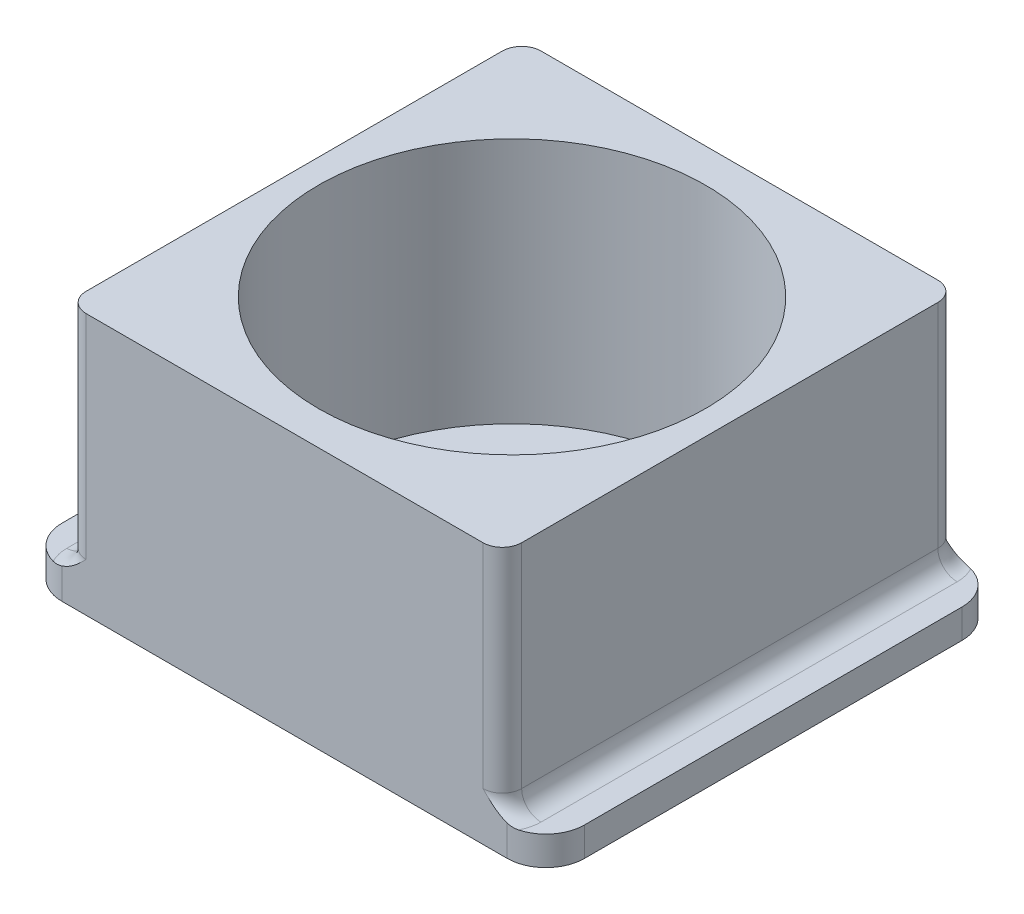
SolidWorks part; units mm, degrees
material "灰铸铁 HT200 (GB)"
ref_plane "前视基准面" through (0, 0, 0) normal (0, 0, 1) x (1, 0, 0)
ref_plane "上视基准面" through (0, 0, 0) normal (0, 1, 0) x (1, 0, 0)
ref_plane "右视基准面" through (0, 0, 0) normal (1, 0, 0) x (0, 0, -1)
sketch "草图1" plane through (0, 0, 0) normal (0, 1, 0) x (1, 0, 0)
  line L1 (-27, -23.5) -> (27, -23.5)
  line L2 (-27, -23.5) -> (-27, 23.5)
  line L3 (-27, 23.5) -> (27, 23.5)
  line L4 (27, -23.5) -> (27, 23.5)
  line L5 (-27, -23.5) -> (27, 23.5) construction
  line L6 (-27, 23.5) -> (27, -23.5) construction
  point P0 (0, 0)
  dimension "D1" = 47
  dimension "D2" = 54
extrude "凸台-拉伸1" add sketch "草图1" along normal mid plane 3
fillet "圆角1" radius 4 4 edges at (27, 0, 23.5) (-27, 0, 23.5) (-27, 0, -23.5) (27, 0, -23.5)
sketch "草图2" plane through (0, 1.5, 0) normal (0, 1, 0) x (1, 0, 0)
  line L1 (-20.5, -23.5) -> (20.5, -23.5)
  line L2 (-22.5, -21.5) -> (-22.5, 21.5)
  line L3 (-20.5, 23.5) -> (20.5, 23.5)
  line L4 (22.5, -21.5) -> (22.5, 21.5)
  line L5 (-22.5, -23.5) -> (22.5, 23.5) construction
  line L6 (-22.5, 23.5) -> (22.5, -23.5) construction
  arc A0 (20.5, -23.5) -> (22.5, -21.5) centre (20.5, -21.5) ccw
  arc A1 (-22.5, 21.5) -> (-20.5, 23.5) centre (-20.5, 21.5) cw
  arc A2 (-20.5, -23.5) -> (-22.5, -21.5) centre (-20.5, -21.5) cw
  arc A3 (20.5, 23.5) -> (22.5, 21.5) centre (20.5, 21.5) cw
  point P0 (0, 0)
  dimension "D3" = 2
  dimension "D1" = 47
  dimension "D2" = 45
extrude "凸台-拉伸2" add sketch "草图2" along normal blind 24
fillet "圆角2" radius 2 6 edges at (-21.9142, 1.5, -22.9142) (-21.9142, 1.5, 22.9142) (21.9142, 1.5, 22.9142) (21.9142, 1.5, -22.9142) (-22.5, 1.5, 0) (22.5, 1.5, 0)
sketch "草图3" plane through (0, 25.5, 0) normal (0, 1, 0) x (1, 0, 0)
  circle A0 centre (0, 0) radius 20
  dimension "D1" = 40
extrude "切除-拉伸1" cut sketch "草图3" against normal blind 25.5009
sketch "草图4" plane through (0, -0.0009, 0) normal (0, 1, 0) x (1, 0, 0)
  circle A0 centre (0, 0) radius 10
  dimension "D1" = 20
extrude "切除-拉伸2" cut sketch "草图4" against normal through all
